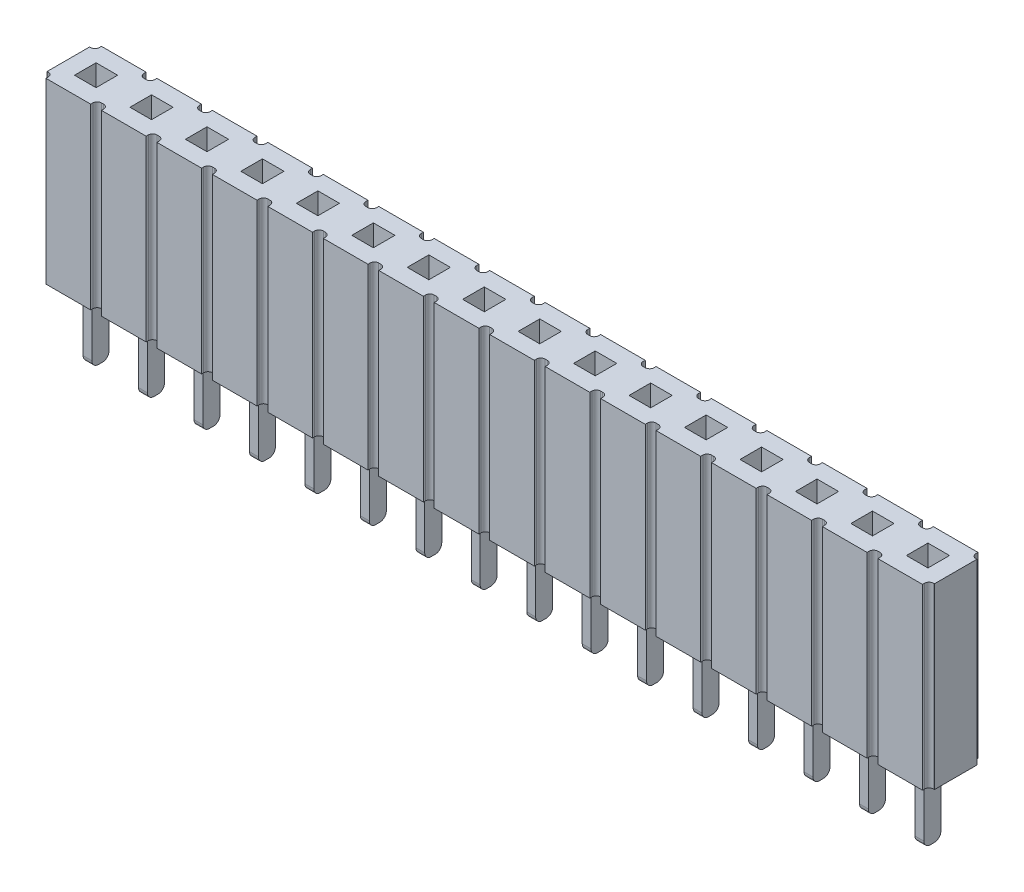
SolidWorks part; units mm, degrees
ref_plane "Front Plane" through (0, 0, 0) normal (0, 0, 1) x (1, 0, 0)
ref_plane "Top Plane" through (0, 0, 0) normal (0, 1, 0) x (1, 0, 0)
ref_plane "Right Plane" through (0, 0, 0) normal (1, 0, 0) x (0, 0, -1)
sketch "Sketch1" plane through (0, 0, 0) normal (0, 0, 1) x (1, 0, 0)
  line L0 (-20.56, 4.13) -> (20.56, 4.13)
  line L1 (-20.56, 4.13) -> (-20.56, -4.13)
  line L2 (20.56, 4.13) -> (20.56, -4.13)
  line L3 (-20.56, -4.13) -> (20.56, -4.13)
  line L4 (-20.56, 4.13) -> (20.56, -4.13) construction
  line L5 (20.56, 4.13) -> (-20.56, -4.13) construction
  point P1 (0, 0)
  dimension "D1" = 8.26
  dimension "D2" = 41.12
extrude "Boss-Extrude1" add sketch "Sketch1" along normal blind 1.285 and the other way blind 1.285
sketch "Sketch3" plane through (0, 4.13, 0) normal (0, 1, 0) x (1, 0, 0)
  line L0 (-0.05, -0.985) -> (0.05, -0.985)
  line L1 (-0.25, -1.185) -> (-0.25, -1.285)
  line L2 (0.25, -1.185) -> (0.25, -1.285)
  line L3 (-0.25, -1.285) -> (0.25, -1.285)
  line L4 (-0.25, -0.985) -> (0.25, -1.285) construction
  line L5 (0.25, -0.985) -> (-0.25, -1.285) construction
  line L8 (20.56, -1.285) -> (-20.56, -1.285) construction
  arc A0 (0.05, -0.985) -> (0.25, -1.185) centre (0.05, -1.185) cw
  arc A1 (-0.25, -1.185) -> (-0.05, -0.985) centre (-0.05, -1.185) cw
  point P1 (0, -1.135)
  dimension "D4" = 0.2
  dimension "D1" = 0.3
  dimension "D2" = 0.5
  dimension "D3" = 0
extrude "Cut-Extrude2" cut sketch "Sketch3" against normal through all
pattern_linear "LPattern2" count 9 spacing 2.57 along (-1, 0, 0) count 9 spacing 2.57 along (1, 0, 0) of "Cut-Extrude2"
mirror "Mirror2" about plane through (0, 0, 0) normal (0, 0, 1) of "LPattern2"
sketch "Sketch4" plane through (0, 4.13, 0) normal (0, 1, 0) x (1, 0, 0)
  line L0 (0.785, -0.5) -> (1.785, -0.5)
  line L1 (0.785, -0.5) -> (0.785, 0.5)
  line L2 (1.785, -0.5) -> (1.785, 0.5)
  line L3 (0.785, 0.5) -> (1.785, 0.5)
  line L4 (0.785, -0.5) -> (1.785, 0.5) construction
  line L5 (1.785, -0.5) -> (0.785, 0.5) construction
  point P1 (1.285, 0)
  dimension "D1" = 1.285
  dimension "D2" = 0
  dimension "D3" = 1
  dimension "D4" = 1
extrude "Cut-Extrude3" cut sketch "Sketch4" against normal blind 8
pattern_linear "LPattern3" count 9 spacing 2.57 along (-1, 0, 0) count 8 spacing 2.57 along (1, 0, 0) of "Cut-Extrude3"
sketch "Sketch5" plane through (0, -4.13, 0) normal (0, -1, 0) x (1, 0, 0)
  line L0 (1.08, -0.395) -> (1.49, -0.395)
  line L1 (1.08, -0.395) -> (1.08, 0.395)
  line L2 (1.49, -0.395) -> (1.49, 0.395)
  line L3 (1.08, 0.395) -> (1.49, 0.395)
  line L4 (1.08, -0.395) -> (1.49, 0.395) construction
  line L5 (1.49, -0.395) -> (1.08, 0.395) construction
  point P1 (1.285, 0)
  dimension "D1" = 0.79
  dimension "D2" = 0.41
  dimension "D3" = 1.285
  dimension "D4" = 0
extrude "Boss-Extrude2" add sketch "Sketch5" along normal blind 3.2
pattern_linear "LPattern6" count 9 spacing 2.57 along (-1, 0, 0) count 8 spacing 2.57 along (1, 0, 0) of "Boss-Extrude2"
fillet "Fillet2" radius 0.3 32 edges at (1.285, -7.33, 0.395) (1.285, -7.33, -0.395) (-19.275, -7.33, -0.395) (-16.705, -7.33, -0.395) (-14.135, -7.33, -0.395) (-11.565, -7.33, -0.395) (-8.995, -7.33, -0.395) (-6.425, -7.33, -0.395) (-3.855, -7.33, -0.395) (-1.285, -7.33, -0.395) (3.855, -7.33, -0.395) (6.425, -7.33, -0.395) (8.995, -7.33, -0.395) (11.565, -7.33, -0.395) (14.135, -7.33, -0.395) (16.705, -7.33, -0.395) (19.275, -7.33, -0.395) (19.275, -7.33, 0.395) (16.705, -7.33, 0.395) (14.135, -7.33, 0.395) (11.565, -7.33, 0.395) (8.995, -7.33, 0.395) (6.425, -7.33, 0.395) (3.855, -7.33, 0.395) (-1.285, -7.33, 0.395) (-3.855, -7.33, 0.395) (-6.425, -7.33, 0.395) (-8.995, -7.33, 0.395) (-11.565, -7.33, 0.395) (-14.135, -7.33, 0.395) (-16.705, -7.33, 0.395) (-19.275, -7.33, 0.395)
